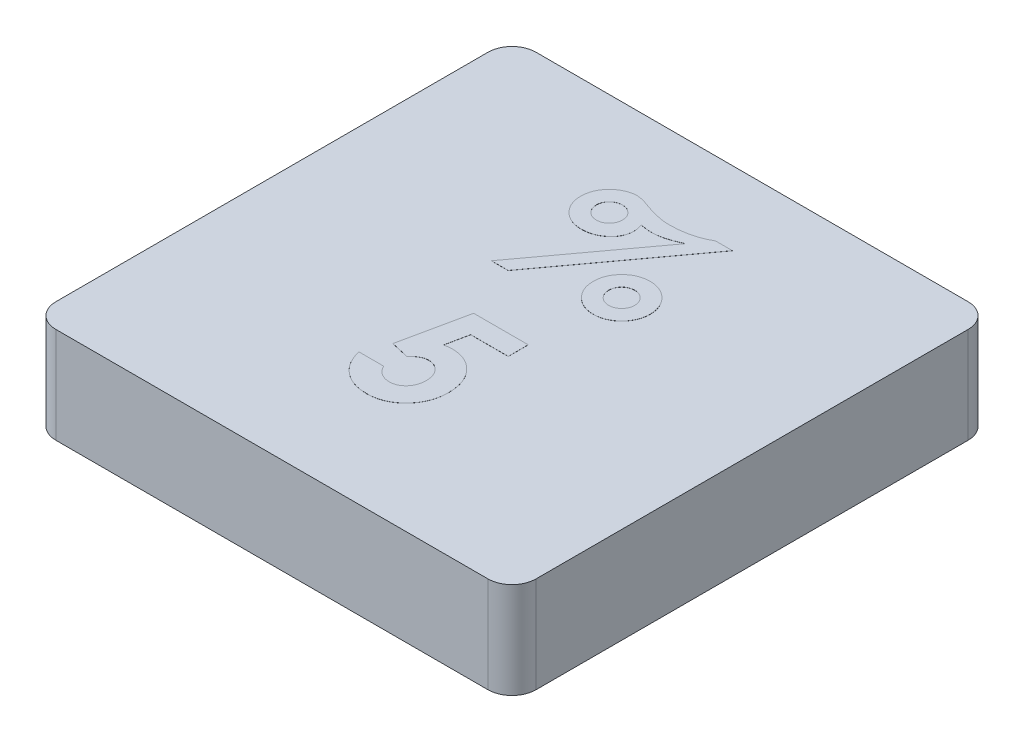
SolidWorks part; units mm, degrees
ref_plane "Front Plane" through (0, 0, 0) normal (0, 0, 1) x (1, 0, 0)
ref_plane "Top Plane" through (0, 0, 0) normal (0, 1, 0) x (1, 0, 0)
ref_plane "Right Plane" through (0, 0, 0) normal (1, 0, 0) x (0, 0, -1)
sketch "Sketch1" plane through (0, 0, 0) normal (0, 1, 0) x (1, 0, 0)
  line L0 (0, 0) -> (12.7, 0)
  line L1 (12.7, 0) -> (12.7, 12.7)
  line L2 (12.7, 12.7) -> (0, 12.7)
  line L3 (0, 12.7) -> (0, 0)
  dimension "D1" = 12.7
  dimension "D2" = 12.7
extrude "Boss-Extrude1" add sketch "Sketch1" along normal blind 2.54
fillet "Fillet1" radius 0.635 4 edges at (0, 1.27, -12.7) (12.7, 1.27, -12.7) (12.7, 1.27, 0) (0, 1.27, 0)
shell "Shell1" thickness 0.635 removed face at (6.35, 0, -6.35)
sketch "Sketch2" plane through (0, 1.905, 0) normal (0, -1, 0) x (-1, 0, 0)
  line L0 (-0.635, 6.35) -> (-12.065, 6.35) construction
  line L1 (-0.635, 12.065) -> (-0.635, 0.635) construction
  line L2 (-12.065, 0.635) -> (-12.065, 12.065) construction
  line L3 (-6.35, 0.635) -> (-6.35, 12.065) construction
  line L4 (-0.635, 0.635) -> (-12.065, 0.635) construction
  line L5 (-12.065, 12.065) -> (-0.635, 12.065) construction
  circle A0 centre (-6.35, 6.35) radius 2.54
  dimension "D1" = 5.08
extrude "Boss-Extrude2" add sketch "Sketch2" along normal up to surface (1.905 mm away) up to face at (6.35, 0, -6.35)
sketch "Sketch4" plane through (0, 2.54, 0) normal (0, 1, 0) x (1, 0, 0)
  line L0 (0, 12.065) -> (0, 0.635) construction
  line L1 (12.065, 12.7) -> (0.635, 12.7) construction
  line L2 (0.635, 0) -> (12.065, 0) construction
  text T0 "<b>5</b>"
  text T1 "<b>%</b>"
  dimension "D1" = 4.445
  dimension "D2" = 5.08
  dimension "D3" = 5.207
  dimension "D4" = 2.7178
extrude "Boss-Extrude4" add sketch "Sketch4" along normal blind 0.0025
